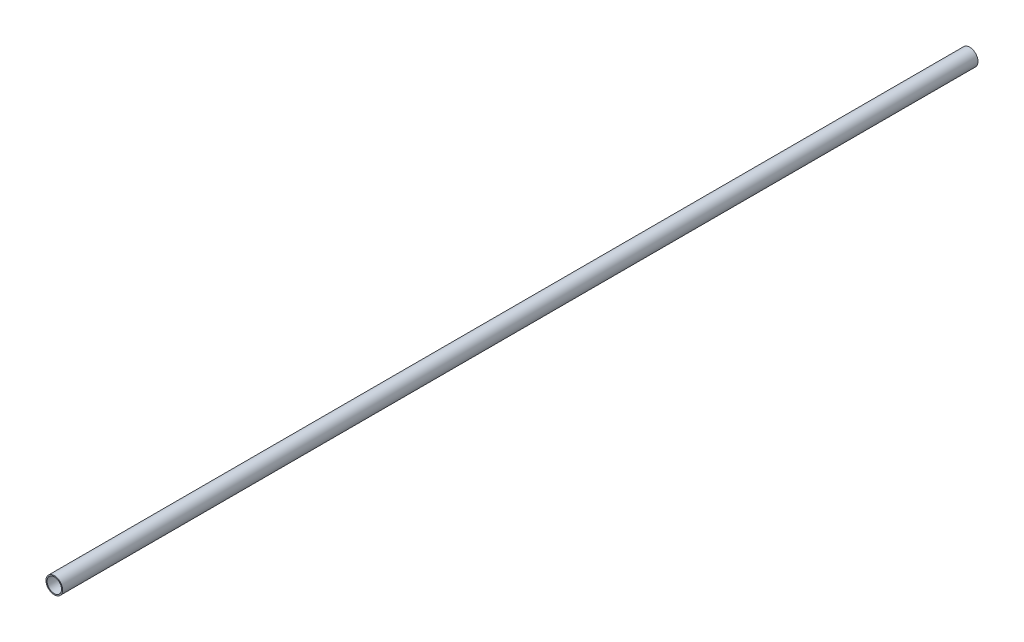
SolidWorks part; units mm, degrees
material "AISI 304"
ref_plane "Front" through (0, 0, 0) normal (0, 0, 1) x (1, 0, 0)
ref_plane "Top" through (0, 0, 0) normal (0, 1, 0) x (1, 0, 0)
ref_plane "Right" through (0, 0, 0) normal (1, 0, 0) x (0, 0, -1)
sketch "Sketch1" plane through (0, 0, 0) normal (0, 0, 1) x (1, 0, 0)
  line L0 (0, 11.049) -> (0, 12.7) construction
  circle A0 centre (0, 0) radius 12.7
  circle A1 centre (0, 0) radius 11.049
  dimension "D1" = 25.4
  dimension "D3" = 1.651
  dimension "D2" = 22.098
extrude "Boss-Extrude1" add sketch "Sketch1" along normal blind 1397
